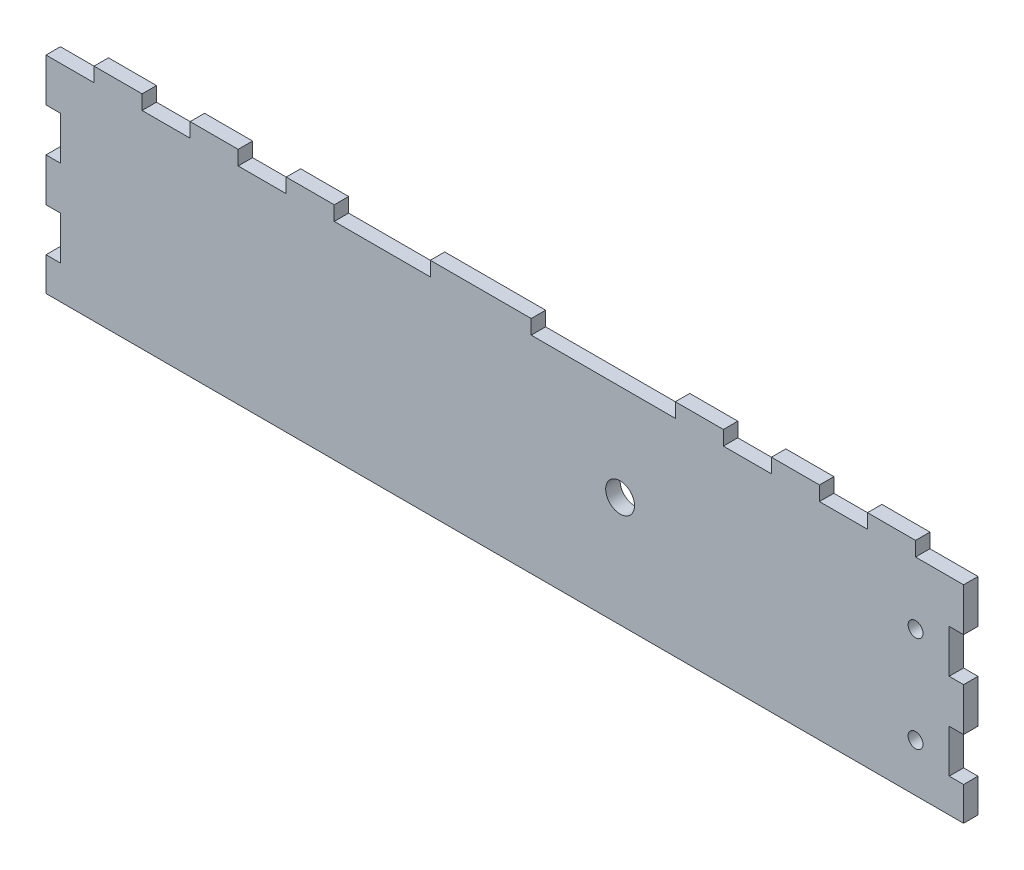
SolidWorks part; units mm, degrees
ref_plane "Front Plane" through (0, 0, 0) normal (0, 0, 1) x (1, 0, 0)
ref_plane "Top Plane" through (0, 0, 0) normal (0, 1, 0) x (1, 0, 0)
ref_plane "Right Plane" through (0, 0, 0) normal (1, 0, 0) x (0, 0, -1)
sketch "Sketch1" plane through (0, 0, 0) normal (0, 0, 1) x (1, 0, 0)
  line L4 (0, 0) -> (191, 0)
  line L5 (191, 0) -> (191, 46)
  line L6 (191, 46) -> (0, 46)
  line L7 (0, 46) -> (0, 0)
  line L8 (0, 0) -> (191, 0)
  line L9 (191, 0) -> (191, 46)
  line L10 (191, 46) -> (0, 46)
  line L11 (0, 46) -> (0, 0)
  circle A0 centre (181, 30) radius 1.55 construction
  circle A1 centre (181, 10) radius 1.55 construction
  circle A2 centre (181, 30) radius 1.55
  circle A3 centre (181, 10) radius 1.55
  dimension "D1" = 0
extrude "Boss-Extrude1" add sketch "Sketch1" along normal blind 3
sketch "Sketch3" plane through (0, 0, 3) normal (0, 0, 1) x (1, 0, 0)
  line L0 (119.5, 46) -> (119.5, 0) construction
  line L1 (119.5, 46) -> (119.5, 0)
  point P2 (119.5, 23)
ref_point "MountPoint-Sus"
sketch "Sketch4" plane through (0, 0, 0) normal (0, 0, -1) x (-1, 0, 0)
  line L0 (-10, 43) -> (-10, 46) construction
  line L1 (-10, 46) -> (0, 46) construction
  line L2 (0, 46) -> (0, 43) construction
  line L3 (0, 43) -> (-10, 43) construction
  line L4 (-30, 43) -> (-30, 46) construction
  line L5 (-30, 46) -> (-20, 46) construction
  line L6 (-20, 46) -> (-20, 43) construction
  line L7 (-20, 43) -> (-30, 43) construction
  line L8 (-50, 43) -> (-50, 46) construction
  line L9 (-50, 46) -> (-40, 46) construction
  line L10 (-40, 46) -> (-40, 43) construction
  line L11 (-40, 43) -> (-50, 43) construction
  line L12 (-60, 43) -> (-80, 43) construction
  line L13 (-80, 43) -> (-80, 46) construction
  line L14 (-80, 46) -> (-60, 46) construction
  line L15 (-60, 46) -> (-60, 43) construction
  line L16 (-131, 43) -> (-131, 46) construction
  line L17 (-131, 46) -> (-101, 46) construction
  line L18 (-101, 46) -> (-101, 43) construction
  line L19 (-101, 43) -> (-131, 43) construction
  line L20 (-151, 43) -> (-151, 46) construction
  line L21 (-151, 46) -> (-141, 46) construction
  line L22 (-141, 46) -> (-141, 43) construction
  line L23 (-141, 43) -> (-151, 43) construction
  line L24 (-171, 43) -> (-171, 46) construction
  line L25 (-171, 46) -> (-161, 46) construction
  line L26 (-161, 46) -> (-161, 43) construction
  line L27 (-161, 43) -> (-171, 43) construction
  line L28 (-191, 46) -> (-181, 46) construction
  line L29 (-181, 46) -> (-181, 43) construction
  line L30 (-181, 43) -> (-191, 43) construction
  line L31 (-191, 43) -> (-191, 46) construction
  line L32 (-10, 43) -> (-10, 46)
  line L33 (-10, 46) -> (0, 46)
  line L34 (0, 46) -> (0, 43)
  line L35 (0, 43) -> (-10, 43)
  line L36 (-30, 43) -> (-30, 46)
  line L37 (-30, 46) -> (-20, 46)
  line L38 (-20, 46) -> (-20, 43)
  line L39 (-20, 43) -> (-30, 43)
  line L40 (-50, 43) -> (-50, 46)
  line L41 (-50, 46) -> (-40, 46)
  line L42 (-40, 46) -> (-40, 43)
  line L43 (-40, 43) -> (-50, 43)
  line L44 (-60, 43) -> (-80, 43)
  line L45 (-80, 43) -> (-80, 46)
  line L46 (-80, 46) -> (-60, 46)
  line L47 (-60, 46) -> (-60, 43)
  line L48 (-131, 43) -> (-131, 46)
  line L49 (-131, 46) -> (-101, 46)
  line L50 (-101, 46) -> (-101, 43)
  line L51 (-101, 43) -> (-131, 43)
  line L52 (-151, 43) -> (-151, 46)
  line L53 (-151, 46) -> (-141, 46)
  line L54 (-141, 46) -> (-141, 43)
  line L55 (-141, 43) -> (-151, 43)
  line L56 (-171, 43) -> (-171, 46)
  line L57 (-171, 46) -> (-161, 46)
  line L58 (-161, 46) -> (-161, 43)
  line L59 (-161, 43) -> (-171, 43)
  line L60 (-191, 46) -> (-181, 46)
  line L61 (-181, 46) -> (-181, 43)
  line L62 (-181, 43) -> (-191, 43)
  line L63 (-191, 43) -> (-191, 46)
extrude "Cut-Extrude1" cut sketch "Sketch4" against normal up to next
sketch "Sketch5" plane through (0, 0, 0) normal (0, 0, -1) x (-1, 0, 0)
  line L4 (0, 34) -> (-3, 34)
  line L5 (0, 25) -> (0, 34)
  line L6 (-3, 25) -> (0, 25)
  line L7 (-3, 34) -> (-3, 25)
  line L8 (0, 34) -> (-3, 34)
  line L9 (0, 25) -> (0, 34)
  line L10 (-3, 25) -> (0, 25)
  line L11 (-3, 34) -> (-3, 25)
  line L12 (-3, 7) -> (0, 7)
  line L13 (0, 7) -> (0, 16)
  line L14 (0, 16) -> (-3, 16)
  line L15 (-3, 16) -> (-3, 7)
  line L16 (-3, 7) -> (0, 7)
  line L17 (0, 7) -> (0, 16)
  line L18 (0, 16) -> (-3, 16)
  line L19 (-3, 16) -> (-3, 7)
  dimension "D1" = 0
  dimension "D2" = 0
extrude "Cut-Extrude2" cut sketch "Sketch5" against normal up to next
sketch "Sketch6" plane through (0, 0, 0) normal (0, 0, -1) x (-1, 0, 0)
  line L0 (-188, 25) -> (-188, 34) construction
  line L1 (-188, 34) -> (-191, 34) construction
  line L2 (-191, 25) -> (-188, 25) construction
  line L3 (-188, 16) -> (-191, 16) construction
  line L4 (-188, 7) -> (-188, 16) construction
  line L5 (-191, 7) -> (-188, 7) construction
  line L6 (-188, 25) -> (-188, 34)
  line L7 (-188, 34) -> (-191, 34)
  line L8 (-191, 25) -> (-188, 25)
  line L9 (-188, 16) -> (-191, 16)
  line L10 (-188, 7) -> (-188, 16)
  line L11 (-191, 7) -> (-188, 7)
  line L40 (-3, 7) -> (-3, 16)
  line L41 (-3, 16) -> (0, 16)
  line L42 (0, 16) -> (0, 25)
  line L43 (0, 25) -> (-3, 25)
  line L44 (-3, 25) -> (-3, 34)
  line L45 (-3, 34) -> (0, 34)
  line L46 (0, 34) -> (0, 43)
  line L47 (0, 43) -> (-10, 43)
  line L48 (-10, 43) -> (-10, 46)
  line L49 (-10, 46) -> (-20, 46)
  line L50 (-20, 46) -> (-20, 43)
  line L51 (-20, 43) -> (-30, 43)
  line L52 (-30, 43) -> (-30, 46)
  line L53 (-30, 46) -> (-40, 46)
  line L54 (-40, 46) -> (-40, 43)
  line L55 (-40, 43) -> (-50, 43)
  line L56 (-50, 43) -> (-50, 46)
  line L57 (-50, 46) -> (-60, 46)
  line L58 (-60, 46) -> (-60, 43)
  line L59 (-60, 43) -> (-80, 43)
  line L60 (-80, 43) -> (-80, 46)
  line L61 (-80, 46) -> (-101, 46)
  line L62 (-101, 46) -> (-101, 43)
  line L63 (-101, 43) -> (-131, 43)
  line L64 (-131, 43) -> (-131, 46)
  line L65 (-131, 46) -> (-141, 46)
  line L66 (-141, 46) -> (-141, 43)
  line L67 (-141, 43) -> (-151, 43)
  line L68 (-151, 43) -> (-151, 46)
  line L69 (-151, 46) -> (-161, 46)
  line L70 (-161, 46) -> (-161, 43)
  line L71 (-161, 43) -> (-171, 43)
  line L72 (-171, 43) -> (-171, 46)
  line L73 (-171, 46) -> (-181, 46)
  line L74 (-181, 46) -> (-181, 43)
  line L75 (-181, 43) -> (-191, 43)
  line L76 (-191, 43) -> (-191, 0)
  line L77 (-191, 0) -> (0, 0)
  line L78 (0, 0) -> (0, 7)
  line L79 (0, 7) -> (-3, 7)
  line L80 (-3, 7) -> (-3, 16)
  line L81 (-3, 16) -> (0, 16)
  line L82 (0, 16) -> (0, 25)
  line L83 (0, 25) -> (-3, 25)
  line L84 (-3, 25) -> (-3, 34)
  line L85 (-3, 34) -> (0, 34)
  line L86 (0, 34) -> (0, 43)
  line L87 (0, 43) -> (-10, 43)
  line L88 (-10, 43) -> (-10, 46)
  line L89 (-10, 46) -> (-20, 46)
  line L90 (-20, 46) -> (-20, 43)
  line L91 (-20, 43) -> (-30, 43)
  line L92 (-30, 43) -> (-30, 46)
  line L93 (-30, 46) -> (-40, 46)
  line L94 (-40, 46) -> (-40, 43)
  line L95 (-40, 43) -> (-50, 43)
  line L96 (-50, 43) -> (-50, 46)
  line L97 (-50, 46) -> (-60, 46)
  line L98 (-60, 46) -> (-60, 43)
  line L99 (-60, 43) -> (-80, 43)
  line L100 (-80, 43) -> (-80, 46)
  line L101 (-80, 46) -> (-101, 46)
  line L102 (-101, 46) -> (-101, 43)
  line L103 (-101, 43) -> (-131, 43)
  line L104 (-131, 43) -> (-131, 46)
  line L105 (-131, 46) -> (-141, 46)
  line L106 (-141, 46) -> (-141, 43)
  line L107 (-141, 43) -> (-151, 43)
  line L108 (-151, 43) -> (-151, 46)
  line L109 (-151, 46) -> (-161, 46)
  line L110 (-161, 46) -> (-161, 43)
  line L111 (-161, 43) -> (-171, 43)
  line L112 (-171, 43) -> (-171, 46)
  line L113 (-171, 46) -> (-181, 46)
  line L114 (-181, 46) -> (-181, 43)
  line L115 (-181, 43) -> (-191, 43)
  line L116 (-191, 43) -> (-191, 0)
  line L117 (-191, 0) -> (0, 0)
  line L118 (0, 0) -> (0, 7)
  line L119 (0, 7) -> (-3, 7)
  line M78 (-191, 43) -> (-191, 0)
  dimension "D1" = 0
extrude "Cut-Extrude3" cut sketch "Sketch6" against normal up to next contours L8 L6 L7 M78 | L11 L10 L9 M78 region at (189.5, 29.5, 0) region at (189.5, 11.5, 0)
sketch "Sketch7" plane through (0, 0, 3) normal (0, 0, 1) x (1, 0, 0)
  circle A0 centre (119.5, 23) radius 3
  point P0 (119.5, 23)
  dimension "D1" = 6
extrude "Cut-Extrude4" cut sketch "Sketch7" against normal up to next
